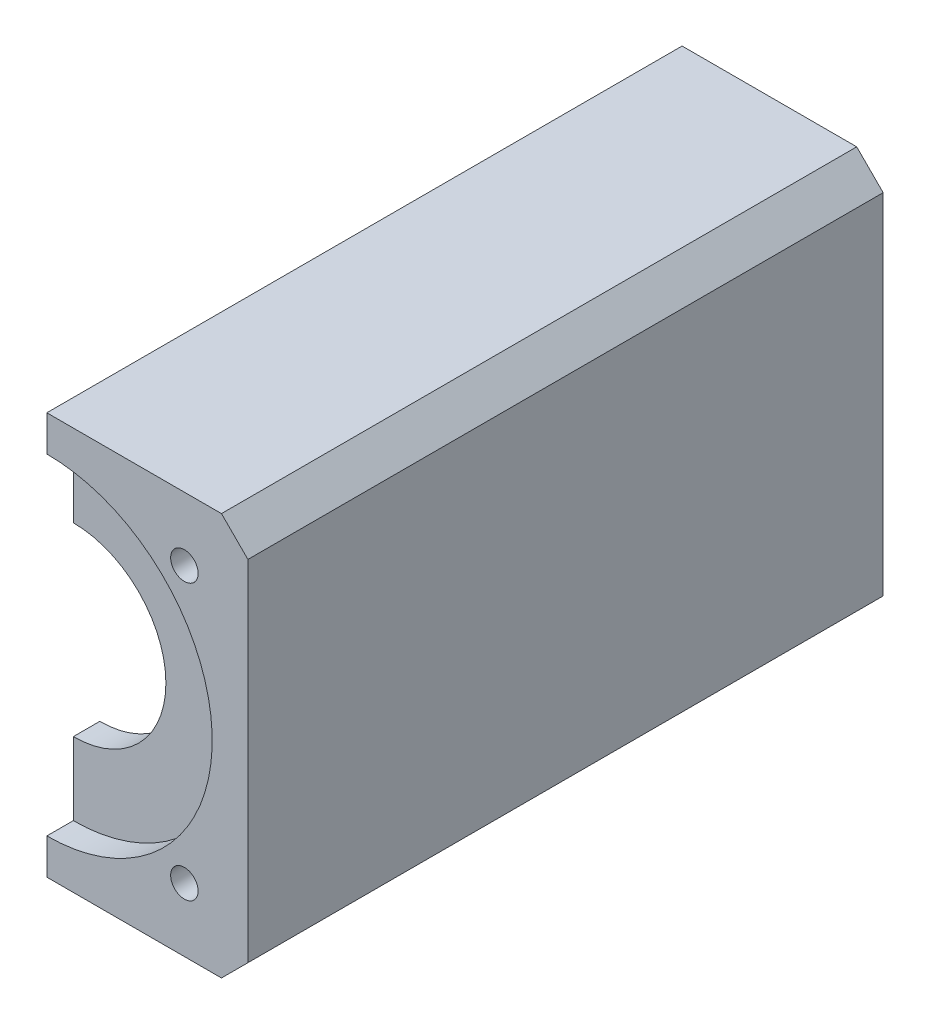
SolidWorks part; units mm, degrees
material "2024-T3"
ref_plane "Front Plane" through (0, 0, 0) normal (0, 0, 1) x (1, 0, 0)
ref_plane "Top Plane" through (0, 0, 0) normal (0, 1, 0) x (1, 0, 0)
ref_plane "Right Plane" through (0, 0, 0) normal (1, 0, 0) x (0, 0, -1)
sketch "Sketch1" plane through (0, 0, 0) normal (0, 0, 1) x (1, 0, 0)
  line L0 (0, 0) -> (41.91, 41.91) construction
  line L1 (0, 0) -> (41.91, 0)
  line L2 (0, 0) -> (0, 41.91)
  line L3 (0, 41.91) -> (41.91, 41.91)
  line L4 (41.91, 0) -> (41.91, 41.91)
  line L5 (4.4493, 37.4607) -> (20.955, 20.955) construction
  circle A0 centre (37.4607, 37.4607) radius 1.6497
  circle A1 centre (37.4607, 4.4493) radius 1.6497
  circle A2 centre (4.4493, 4.4493) radius 1.6497
  circle A3 centre (4.4493, 37.4607) radius 1.6497
  circle A4 centre (20.955, 20.955) radius 11.1125
  point P7 (20.955, 20.955)
  point P17 (20.955, 20.955)
  dimension "D3" = 3.2995
  dimension "D7" = 22.225
  dimension "D1" = 41.91
  dimension "D2" = 41.91
  dimension "D4" = 23.3426
  dimension "D6" = 23.3426
  dimension "D5" = 4
extrude "Boss-Extrude1" add sketch "Sketch1" along normal blind 6.35
sketch "Sketch2" plane through (0, 0, 6.35) normal (0, 0, 1) x (1, 0, 0)
  circle A0 centre (20.955, 20.955) radius 27.7876
  circle A1 centre (20.955, 20.955) radius 62.5657
  dimension "D1" = 55.5752
extrude "Cut-Extrude1" cut sketch "Sketch2" against normal through all
sketch "Sketch3" plane through (0, 0, 6.35) normal (0, 0, 1) x (1, 0, 0)
  circle A0 centre (20.955, 20.955) radius 19.8438
  dimension "D1" = 39.6875
extrude "Cut-Extrude2" cut sketch "Sketch3" against normal blind 3.175
sketch "Sketch4" plane through (0, 0, 6.35) normal (0, 0, 1) x (1, 0, 0)
  line L0 (0, 39.2043) -> (0, 2.7057) construction
  line L1 (-3.175, 45.085) -> (45.085, 45.085)
  line L2 (-3.175, 45.085) -> (-3.175, -3.175)
  line L3 (-3.175, -3.175) -> (45.085, -3.175)
  line L4 (45.085, 45.085) -> (45.085, -3.175)
  line L5 (39.2043, 41.91) -> (2.7057, 41.91) construction
  line L6 (41.91, 2.7057) -> (41.91, 39.2043) construction
  line L7 (2.7057, 0) -> (39.2043, 0) construction
  line L12 (0, 39.2043) -> (0, 2.7057)
  line L13 (2.7057, 0) -> (39.2043, 0)
  line L14 (41.91, 2.7057) -> (41.91, 39.2043)
  line L15 (39.2043, 41.91) -> (2.7057, 41.91)
  line L16 (0, 39.2043) -> (0, 2.7057)
  line L17 (2.7057, 0) -> (39.2043, 0)
  line L18 (41.91, 2.7057) -> (41.91, 39.2043)
  line L19 (39.2043, 41.91) -> (2.7057, 41.91)
  arc A4 (2.7057, 41.91) -> (0, 39.2043) centre (20.955, 20.955) ccw
  arc A5 (0, 2.7057) -> (2.7057, 0) centre (20.955, 20.955) ccw
  arc A6 (39.2043, 0) -> (41.91, 2.7057) centre (20.955, 20.955) ccw
  arc A7 (41.91, 39.2043) -> (39.2043, 41.91) centre (20.955, 20.955) ccw
  arc A8 (2.7057, 41.91) -> (0, 39.2043) centre (20.955, 20.955) ccw
  arc A9 (0, 2.7057) -> (2.7057, 0) centre (20.955, 20.955) ccw
  arc A10 (39.2043, 0) -> (41.91, 2.7057) centre (20.955, 20.955) ccw
  arc A11 (41.91, 39.2043) -> (39.2043, 41.91) centre (20.955, 20.955) ccw
  dimension "D1" = 3.175
  dimension "D2" = 3.175
  dimension "D3" = 3.175
  dimension "D4" = 3.175
  dimension "D5" = 0
extrude "Boss-Extrude2" add sketch "Sketch4" against normal up to surface (6.35 mm away) up to face at (6.099, 4.4493, 0)
ref_plane "Plane1" through (20.955, 0, 0) normal (1, 0, 0) x (0, 0, -1)
sketch "Sketch5" plane through (-3.175, 0, 0) normal (-1, 0, 0) x (0, 0, 1)
  line L4 (6.35, 45.085) -> (0, 45.085)
  line L5 (0, 45.085) -> (0, -3.175)
  line L6 (0, -3.175) -> (6.35, -3.175)
  line L7 (6.35, -3.175) -> (6.35, 45.085)
  line L8 (6.35, 45.085) -> (0, 45.085)
  line L9 (0, 45.085) -> (0, -3.175)
  line L10 (0, -3.175) -> (6.35, -3.175)
  line L11 (6.35, -3.175) -> (6.35, 45.085)
  dimension "D1" = 0
extrude "Cut-Extrude3" cut sketch "Sketch5" against normal up to surface (24.13 mm away) up to plane "Plane1"
sketch "Sketch6" plane through (0, 0, 0) normal (0, 0, -1) x (-1, 0, 0)
  line L0 (-45.085, -3.175) -> (-45.085, 45.085) construction
  line L1 (-20.955, -3.175) -> (-45.085, -3.175)
  line L2 (-20.955, -3.175) -> (-20.955, 0)
  line L3 (-20.955, 0) -> (-45.085, 0)
  line L4 (-45.085, -3.175) -> (-45.085, 0)
  line L5 (-45.085, 45.085) -> (-20.955, 45.085) construction
  line L6 (-45.085, -3.175) -> (-41.91, -3.175)
  line L7 (-45.085, -3.175) -> (-45.085, 45.085)
  line L8 (-45.085, 45.085) -> (-41.91, 45.085)
  line L9 (-41.91, -3.175) -> (-41.91, 45.085)
  line L10 (-20.955, 45.085) -> (-20.955, 32.0675) construction
  line L11 (-45.085, 45.085) -> (-20.955, 45.085)
  line L12 (-45.085, 45.085) -> (-45.085, 41.91)
  line L13 (-45.085, 41.91) -> (-20.955, 41.91)
  line L14 (-20.955, 45.085) -> (-20.955, 41.91)
  line M1 (-20.955, 32.0675) -> (-20.955, 45.085)
  line M2 (-20.955, 45.085) -> (-45.085, 45.085)
  line M3 (-45.085, 45.085) -> (-45.085, -3.175)
  line M4 (-45.085, -3.175) -> (-20.955, -3.175)
  line M5 (-20.955, -3.175) -> (-20.955, 9.8425)
  dimension "D1" = 3.175
  dimension "D2" = 3.175
  dimension "D3" = 3.175
extrude "Boss-Extrude3" add sketch "Sketch6" along normal blind 57.1754 contours L9 L1 L3 M5 | L9 L3 M4 M3 | L13 L7 L3 L9 | L13 L9 M3 M2 | L9 L13 M1 M2 region at (31.4325, -1.5875, 0) region at (43.4975, -1.5875, 0) region at (43.4975, 20.955, 0) region at (43.4975, 43.4975, 0) region at (31.4325, 43.4975, 0)
sketch "Sketch8" plane through (0, 0, -57.1754) normal (0, 0, -1) x (-1, 0, 0)
  line L1 (-45.085, 45.085) -> (-20.955, 45.085)
  line L2 (-45.085, 45.085) -> (-45.085, -3.175)
  line L3 (-45.085, -3.175) -> (-20.955, -3.175)
  line L4 (-20.955, 45.085) -> (-20.955, -3.175)
extrude "Boss-Extrude4" add sketch "Sketch8" along normal blind 6.35
sketch "Sketch10" plane through (0, 0, 0) normal (0, 1, 0) x (1, 0, 0)
  line L0 (20.955, 15.2654) -> (41.91, 15.2654)
  line L4 (20.955, 0) -> (41.91, 0)
  line L5 (41.91, 0) -> (41.91, 57.1754)
  line L6 (41.91, 57.1754) -> (20.955, 57.1754)
  line L7 (20.955, 57.1754) -> (20.955, 0)
  line L8 (20.955, 0) -> (41.91, 0)
  line L9 (41.91, 0) -> (41.91, 57.1754)
  line L10 (41.91, 57.1754) -> (20.955, 57.1754)
  line L11 (20.955, 57.1754) -> (20.955, 0)
  line M6 (41.91, 0) -> (41.91, 57.1754)
  line M7 (41.91, 57.1754) -> (20.955, 57.1754)
  line M8 (20.955, 57.1754) -> (20.955, 0)
  dimension "D2" = 41.91
  dimension "D1" = 0
extrude "Cut-Extrude6" cut sketch "Sketch10" against normal through all contours L0 M8 M6 M7 region at (31.4325, 0, -36.2204)
chamfer "Chamfer1" distance 3.175 angle 45 2 edges at (45.085, 45.085, -28.5877) (45.085, -3.175, -28.5877)
sketch "Sketch11" plane through (20.955, 0, 0) normal (-1, 0, 0) x (0, 0, 1)
  circle A1 centre (0, 41.91) radius 1.5875
  circle A2 centre (0, 0) radius 1.5875
  dimension "D1" = 3.175
extrude "Cut-Extrude7" cut sketch "Sketch11" against normal up to surface (20.955 mm away) up to face at (41.91, 12.9117, -24.1469)
fillet "Fillet1" radius 6.6675 1 edges
sketch "Sketch13" plane through (0, 0, -63.5254) normal (0, 0, -1) x (-1, 0, 0)
  line L6 (-20.955, 45.085) -> (-41.91, 45.085)
  line L7 (-41.91, 45.085) -> (-45.085, 41.91)
  line L8 (-45.085, 41.91) -> (-45.085, 0)
  line L9 (-45.085, 0) -> (-41.91, -3.175)
  line L10 (-41.91, -3.175) -> (-20.955, -3.175)
  line L11 (-20.955, -3.175) -> (-20.955, 45.085)
  line L12 (-20.955, 45.085) -> (-41.91, 45.085)
  line L13 (-41.91, 45.085) -> (-45.085, 41.91)
  line L14 (-45.085, 41.91) -> (-45.085, 0)
  line L15 (-45.085, 0) -> (-41.91, -3.175)
  line L16 (-41.91, -3.175) -> (-20.955, -3.175)
  line L17 (-20.955, -3.175) -> (-20.955, 45.085)
  dimension "D1" = 0
extrude "Boss-Extrude6" add sketch "Sketch13" along normal blind 6.35
sketch "Sketch14" plane through (0, 0, -69.8754) normal (0, 0, -1) x (-1, 0, 0)
  line L0 (-20.955, -3.175) -> (-20.955, 45.085) construction
  line L1 (-6.6675, 6.6675) -> (-35.2425, 6.6675)
  line L2 (-6.6675, 6.6675) -> (-6.6675, 35.2425)
  line L3 (-6.6675, 35.2425) -> (-35.2425, 35.2425)
  line L4 (-35.2425, 6.6675) -> (-35.2425, 35.2425)
  line L5 (-6.6675, 6.6675) -> (-35.2425, 35.2425) construction
  line L6 (-6.6675, 35.2425) -> (-35.2425, 6.6675) construction
  line L7 (-43.4975, 43.4975) -> (-35.2425, 35.2425) construction
  line L8 (-41.91, 45.085) -> (-45.085, 41.91) construction
  point P0 (-20.955, 20.955)
  dimension "D1" = 28.575
extrude "Cut-Extrude8" cut sketch "Sketch14" against normal blind 12.7
chamfer "Chamfer2" distance 1.5875 angle 45 3 edges at (28.0988, 35.2425, -69.8754) (35.2425, 20.955, -69.8754) (28.0988, 6.6675, -69.8754)
